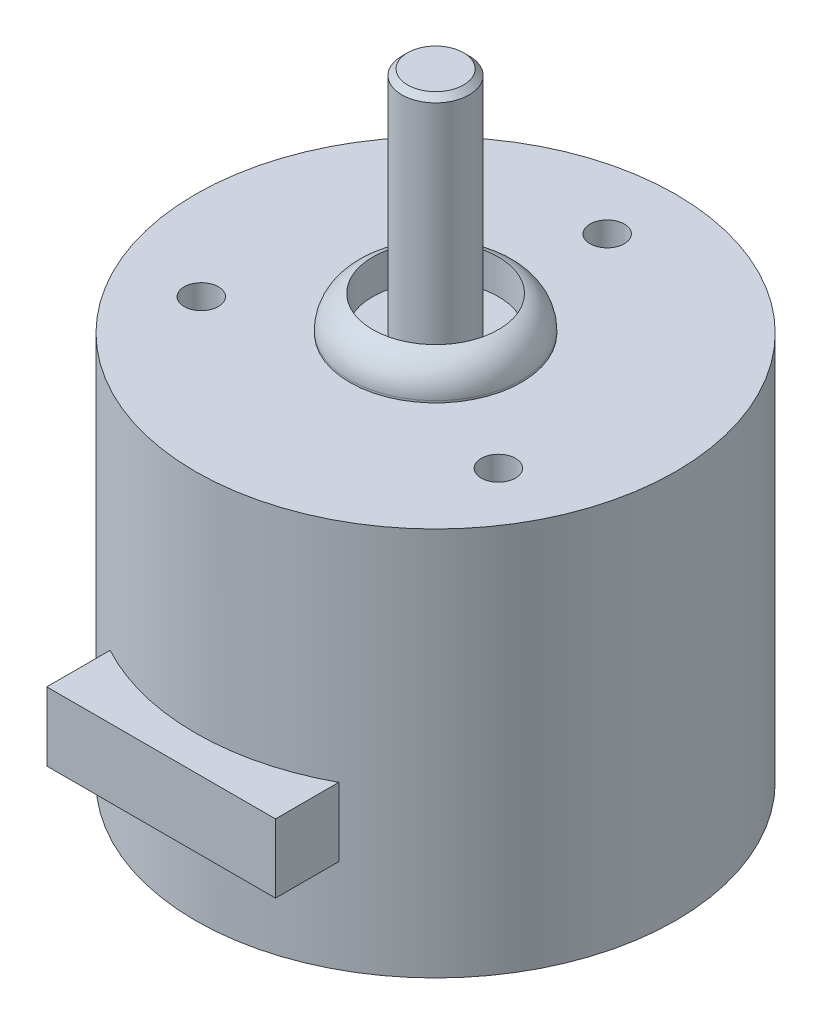
SolidWorks part; units mm, degrees
ref_plane "Front Plane" through (0, 0, 0) normal (0, 0, 1) x (1, 0, 0)
ref_plane "Top Plane" through (0, 0, 0) normal (0, 1, 0) x (1, 0, 0)
ref_plane "Right Plane" through (0, 0, 0) normal (1, 0, 0) x (0, 0, -1)
sketch "Sketch1" plane through (0, 0, 0) normal (0, 1, 0) x (1, 0, 0)
  line L0 (0, 40.1578) -> (0, -40.1578) construction
  line L1 (-36.1819, 0) -> (33.7463, 0) construction
  line L2 (-10, -18.4662) -> (-10, -24)
  line L3 (-10, -24) -> (10, -24)
  line L4 (10, -18.4662) -> (10, -24)
  line L5 (0, 0) -> (-25.9808, -15) construction
  line L6 (0, 0) -> (25.9808, -15) construction
  circle A0 centre (0, 0) radius 21
  circle A1 centre (0, 0) radius 5.5
  circle A2 centre (0, 0) radius 2.945
  circle A3 centre (0, 0) radius 7.5
  circle A4 centre (0, 0) radius 15 construction
  circle A5 centre (0, 15) radius 1.5
  circle A6 centre (-12.9904, -7.5) radius 1.5
  circle A7 centre (12.9904, -7.5) radius 1.5
  point P10 (0, 0)
  point P15 (0, -24)
  point P19 (-12.9904, -7.5)
  point P22 (12.9904, -7.5)
  dimension "D1" = 42
  dimension "D2" = 20
  dimension "D4" = 15
  dimension "D5" = 11
  dimension "D6" = 5.89
  dimension "D7" = 30
  dimension "D8" = 120
  dimension "D10" = 3
  dimension "D11" = 3
  dimension "D12" = 3
  dimension "D3" = 24
  dimension "D9" = 120
extrude "Boss-Extrude1" add sketch "Sketch1" along normal mid plane 34 contours A2 | A1 A2 | A3 A1 | A0 A7 A6 A5 A3 | A6 | A7 | A5 region at (-10.4431, 0, -17.5313) region at (-5.3444, 0, 0) region at (0, 0, 0) region at (-7.2879, 0, 0) region at (0, 0, -15) region at (-12.9904, 0, 7.5) region at (12.9904, 0, 7.5)
extrude "Cut-Extrude1" cut sketch "Sketch1<3>" against normal blind 10 from surface contours A6 | A7 | A5 region at (0, 0, -15) region at (-12.9904, 0, 7.5) region at (12.9904, 0, 7.5) starting at face at (0, 17, 21)
sketch "Sketch1<3>" plane through (0, 0, 0) normal (0, 1, 0) x (1, 0, 0) same geometry as "Sketch1"
extrude "Boss-Extrude2" add sketch "Sketch1<4>" along normal blind 3 from surface contours A3 A1 region at (-7.2879, 0, 0) starting at face at (-12.9904, 17, 9)
sketch "Sketch1<4>" plane through (0, 0, 0) normal (0, 1, 0) x (1, 0, 0) same geometry as "Sketch1"
fillet "Fillet1" radius 3 1 edges at (0, 20, 7.5)
extrude "Boss-Extrude3" add sketch "Sketch1<5>" along normal blind 20 from surface contours A2 region at (0, 0, 0) starting at face at (0, 17, 7.5)
sketch "Sketch1<5>" plane through (0, 0, 0) normal (0, 1, 0) x (1, 0, 0) same geometry as "Sketch1"
extrude "Boss-Extrude4" add sketch "Sketch1<8>" along normal blind 6 from offset 8.8 contours A0 L2 L3 L4 region at (0, 0, 22.0152) offset against normal yes
sketch "Sketch1<8>" plane through (0, 0, 0) normal (0, 1, 0) x (1, 0, 0) same geometry as "Sketch1"
chamfer "Chamfer1" distance 0.5 angle 45 1 edges at (0, 37, 2.945)
